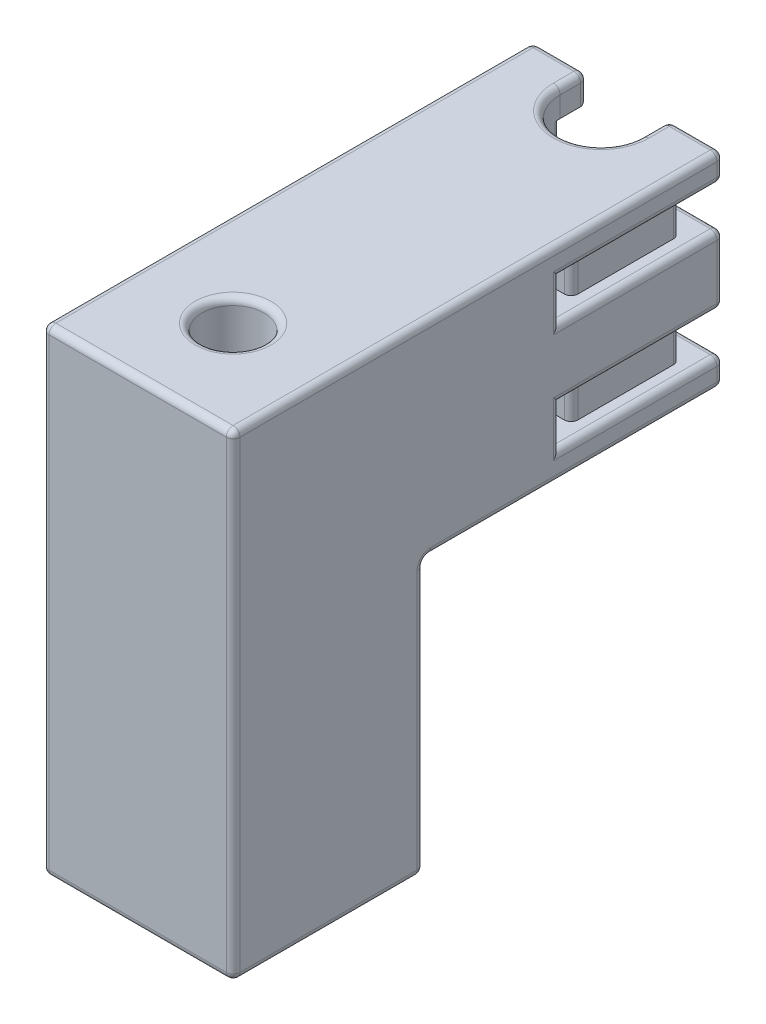
SolidWorks part; units mm, degrees
ref_plane "Front Plane" through (0, 0, 0) normal (0, 0, 1) x (1, 0, 0)
ref_plane "Top Plane" through (0, 0, 0) normal (0, 1, 0) x (1, 0, 0)
ref_plane "Right Plane" through (0, 0, 0) normal (1, 0, 0) x (0, 0, -1)
sketch "Sketch1" plane through (0, 0, 0) normal (0, 1, 0) x (1, 0, 0)
  line L0 (0, 20.9536) -> (0, -51.2812) construction
  line L1 (-31.5295, 0) -> (37.7731, 0) construction
  line L3 (-7, -34) -> (7, -34)
  line L4 (-7, -34) -> (-7, -20)
  line L5 (-7, -20) -> (7, -20)
  line L6 (7, -34) -> (7, -20)
  line L7 (-7, -34) -> (7, -20) construction
  line L8 (-7, -20) -> (7, -34) construction
  point P5 (0, -27)
  dimension "D1" = 14
  dimension "D2" = 14
  dimension "D3" = 20
extrude "Boss-Extrude1" add sketch "Sketch1" along normal blind 20
sketch "Sketch3" plane through (0, 20, 0) normal (0, 1, 0) x (1, 0, 0)
  line L0 (0, 16.3494) -> (0, -50.3764) construction
  line L2 (-7, -34) -> (7, -34)
  line L3 (-7, -34) -> (-7, 2)
  line L4 (-7, 2) -> (7, 2)
  line L5 (7, -34) -> (7, 2)
  dimension "D1" = 14
  dimension "D2" = 36
extrude "Boss-Extrude2" add sketch "Sketch3" along normal blind 15
sketch "Sketch4" plane through (0, 35, 0) normal (0, 1, 0) x (1, 0, 0)
  line L0 (-7.8841, 0) -> (8.2056, 0) construction
  line L1 (-3, 0) -> (-3, 2)
  line L2 (7, 2) -> (-7, 2) construction
  line L3 (3, 0) -> (3, 2)
  line L4 (3, 2) -> (-3, 2)
  arc A0 (-3, 0) -> (3, 0) centre (0, 0) ccw
  dimension "D1" = 6
extrude "Cut-Extrude1" cut sketch "Sketch4" against normal through all both and the other way through all
sketch "Sketch5" plane through (7, 0, 0) normal (1, 0, 0) x (0, 0, -1)
  line L0 (2, 35) -> (2, 20) construction
  line L1 (2, 33) -> (0, 33)
  line L2 (2, 33) -> (2, 30)
  line L3 (2, 30) -> (0, 30)
  line L4 (0, 33) -> (0, 30)
  line L5 (-34, 35) -> (2, 35) construction
  line L6 (-38.989, 27.5) -> (15.3579, 27.5) construction
  line L7 (0, 22) -> (0, 25)
  line L8 (2, 22) -> (2, 25)
  line L9 (2, 25) -> (0, 25)
  line L10 (2, 22) -> (0, 22)
  line L11 (-4, 39.6976) -> (-4, 16.0859) construction
  line L13 (-8, 22) -> (-8, 25)
  line L14 (-10, 22) -> (-8, 22)
  line L15 (-10, 22) -> (-10, 25)
  line L16 (-10, 25) -> (-8, 25)
  line L17 (-8, 33) -> (-8, 30)
  line L18 (-10, 30) -> (-8, 30)
  line L19 (-10, 33) -> (-10, 30)
  line L20 (-10, 33) -> (-8, 33)
  point P10 (2, 27.5)
  dimension "D1" = 3
  dimension "D2" = 2
  dimension "D3" = 2
  dimension "D4" = 6
extrude "Cut-Extrude2" cut sketch "Sketch5" against normal through all both
sketch "Sketch6" plane through (0, 0, 0) normal (0, 0, -1) x (-1, 0, 0)
  line L0 (-3, 30) -> (-7, 30) construction
  line L1 (-7, 33) -> (-5.8, 33)
  line L2 (-7, 33) -> (-7, 30)
  line L3 (-7, 30) -> (-5.8, 30)
  line L4 (-5.8, 33) -> (-5.8, 30)
  line L5 (0, 37.0199) -> (0, -11.7144) construction
  line L6 (7, 30) -> (5.8, 30)
  line L7 (5.8, 33) -> (5.8, 30)
  line L8 (7, 33) -> (5.8, 33)
  line L9 (7, 33) -> (7, 30)
  line L10 (-7, 25) -> (-7, 22) construction
  line L11 (-7, 25) -> (-5.8, 25)
  line L12 (-7, 25) -> (-7, 22)
  line L13 (-7, 22) -> (-5.8, 22)
  line L14 (-5.8, 25) -> (-5.8, 22)
  line L15 (-3, 25) -> (-7, 25) construction
  line L16 (-3, 22) -> (-7, 22) construction
  line L17 (7, 25) -> (7, 22)
  line L18 (7, 22) -> (5.8, 22)
  line L19 (5.8, 25) -> (5.8, 22)
  line L20 (7, 25) -> (5.8, 25)
  dimension "D1" = 1.2
  dimension "D2" = 1.2
extrude "Cut-Extrude3" cut sketch "Sketch6" against normal up to next
sketch "Sketch7" plane through (0, 0, 0) normal (0, -1, 0) x (1, 0, 0)
  line L0 (0, 34.6651) -> (0, 17.8755) construction
  line L1 (-8.4882, 27) -> (8.1753, 27) construction
  line L2 (7, 34) -> (7, 20) construction
  circle A1 centre (0, 27) radius 3.175
  point P7 (7, 27)
  dimension "D1" = 6.35
extrude "Cut-Extrude4" cut sketch "Sketch7" against normal blind 4.699
sketch "Sketch8" plane through (0, 4.699, 0) normal (0, -1, 0) x (1, 0, 0)
  circle A0 centre (0, 27) radius 2.286
  dimension "D1" = 4.572
extrude "Cut-Extrude5" cut sketch "Sketch8" against normal through all
fillet "Fillet1" radius 0.5 57 edges at (-3, 21, -2) (-5, 22, -2) (5, 22, -2) (3, 21, -2) (-5, 30, -2) (-5, 25, -2) (-3, 27.5, -2) (-5, 33, -2) (-3, 34, -2) (3, 34, -2) (5, 33, -2) (5, 30, -2) (3, 27.5, -2) (5, 25, -2) (-5, 20, -2) (5, 20, -2) (3, 20, -1) (0, 20, 3) (-3, 20, -1) (0, 20, 20) (0, 0, 20) (7, 20, 9) (7, 10, 20) (7, 0, 27) (7, 34, -2) (7, 33, 4) (7, 31.5, 10) (7, 30, 4) (7, 27.5, -2) (7, 25, 4) (7, 23.5, 10) (7, 22, 4) (7, 21, -2) (7, 17.5, 34) (0, 0, 34) (-7, 31.5, 10) (-7, 33, 4) (-7, 34, -2) (-7, 17.5, 34) (-7, 0, 27) (-7, 10, 20) (-7, 20, 9) (-7, 21, -2) (-7, 22, 4) (-7, 23.5, 10) (-7, 25, 4) (-7, 27.5, -2) (-7, 30, 4) (3, 35, -1) (5, 35, -2) (7, 35, 16) (0, 35, 34) (-7, 35, 16) (-5, 35, -2) (-3, 35, -1) (0, 35, 3) (0, 35, 24.714)
fillet "Fillet2" radius 0.5 12 edges at (-5.8, 23.5, 8) (-5.8, 31.5, 8) (-5.8, 23.5, 0) (-3, 23.5, 0) (-5.8, 31.5, 0) (-3, 31.5, 0) (3, 31.5, 0) (3, 23.5, 0) (5.8, 23.5, 0) (5.8, 31.5, 0) (5.8, 31.5, 8) (5.8, 23.5, 8)
draft "Draft1" type of draft neutral plane draft angle 4 faces to draft 1 face at (0, 4.699, 23.825) neutral plane through (0, 0, 0) neutral plane normal (0, -1, 0) parameters "D1"=4
